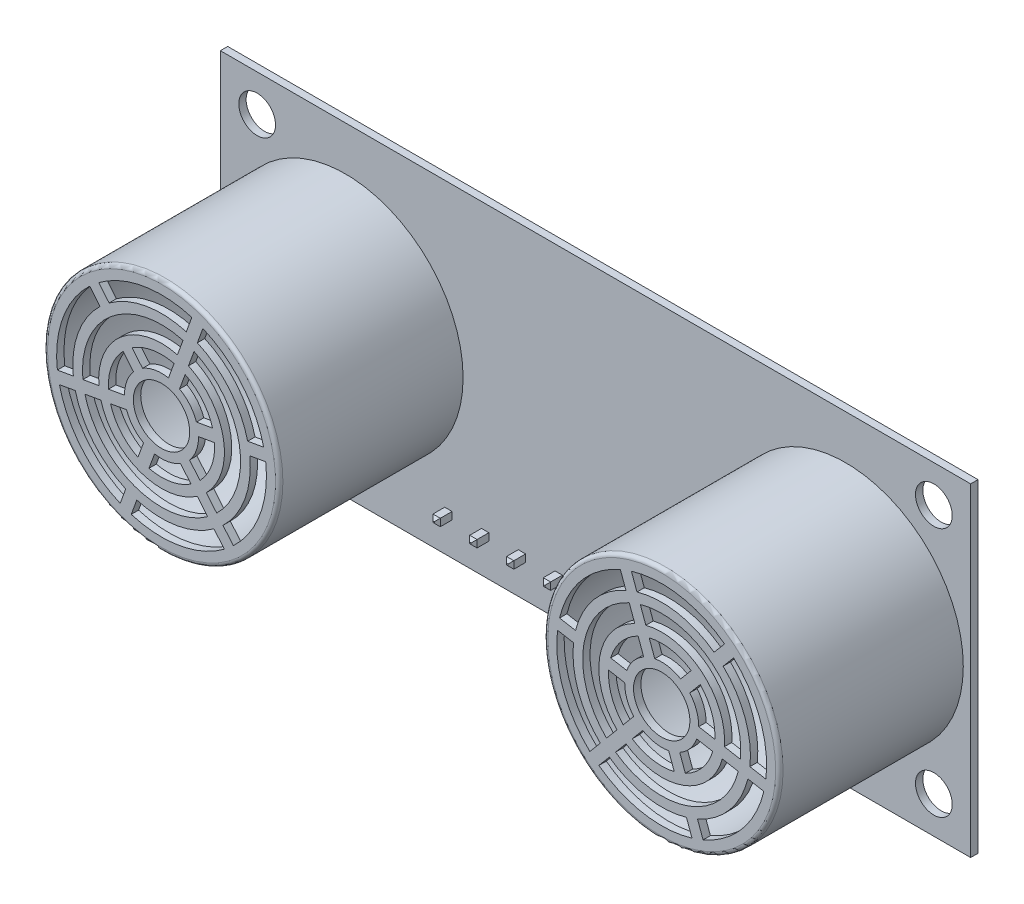
SolidWorks part; units mm, degrees
ref_plane "Спереди" through (0, 0, 0) normal (0, 0, 1) x (1, 0, 0)
ref_plane "Сверху" through (0, 0, 0) normal (0, 1, 0) x (1, 0, 0)
ref_plane "Справа" through (0, 0, 0) normal (1, 0, 0) x (0, 0, -1)
sketch "Эскиз1" plane through (0, 0, 0) normal (0, 0, 1) x (1, 0, 0)
  line L0 (-25.5, 0) -> (25.5, 0) construction
  line L1 (-25.5, -11) -> (25.5, -11)
  line L2 (-25.5, -11) -> (-25.5, 11)
  line L3 (-25.5, 11) -> (25.5, 11)
  line L4 (25.5, -11) -> (25.5, 11)
  line L5 (0, 11) -> (0, -11) construction
  circle A0 centre (-23, 8.5) radius 1.25
  circle A1 centre (-23, -8.5) radius 1.25
  circle A2 centre (23, 8.5) radius 1.25
  circle A3 centre (23, -8.5) radius 1.25
  point P0 (0, 0)
  point P8 (0, 0)
  dimension "D5" = 2.5
  dimension "D1" = 22
  dimension "D2" = 51
  dimension "D3" = 17
  dimension "D4" = 46
extrude "Бобышка-Вытянуть1" add sketch "Эскиз1" against normal blind 0.5
sketch "Эскиз2" plane through (0, 0, 0) normal (0, 0, 1) x (1, 0, 0)
  line L0 (-17, 0) -> (17, 0) construction
  circle A0 centre (-17, 0) radius 8
  dimension "D1" = 16
  dimension "D2" = 34
extrude "Бобышка-Вытянуть2" add sketch "Эскиз2" along normal offset from surface (12.5 mm away) 13 separate body up to face at (24.25, -8.5, -0.5)
shell "Оболочка1" thickness 0.5 removed face at (-9, 0, 0)
sketch "Эскиз3" plane through (0, 0, 12.5) normal (0, 0, 1) x (1, 0, 0)
  circle A1 centre (-17, 0) radius 6.0315
  circle A3 centre (-17, 0) radius 2.5149
  circle A4 centre (-17, 0) radius 4.2741
extrude "Вырез-Вытянуть-Тонкостенный1" cut sketch "Эскиз3" against normal up to next (0.5 mm away) thin contours A4 | A1 | A3 thin type one direction wall 1.1
sketch "Эскиз4" plane through (0, 0, 12.5) normal (0, 0, 1) x (1, 0, 0)
  line L0 (-17, 0) -> (-12.416, -5.463)
  line L1 (-17, 0) -> (-13.44, 0.6277)
  line L2 (-11.7075, 0.9332) -> (-9.9769, 1.2384)
  line L3 (-25.5, -11) -> (25.5, -11) construction
  circle A1 centre (-17, 0) radius 7.1315 construction
  circle A2 centre (-17, 0) radius 3.6149 construction
  circle A4 centre (-17, 0) radius 5.3741 construction
  dimension "D1" = 60
  dimension "D2" = 10
extrude "Вытянуть-Тонкостенный3" add sketch "Эскиз4" against normal blind 0.5 thin thin type mid plane wall 0.8
pattern_circular "Круговой массив2" count 3 over 360 about axis through (-17, 0, 0) along (0, 0, 1) of "Вытянуть-Тонкостенный3"
fillet "Скругление1" radius 0.25 1 edges at (-25, 0, 12.5)
sketch "Эскиз5" plane through (0, 0, 12.5) normal (0, 0, 1) x (1, 0, 0)
  circle A0 centre (-17, 0) radius 1.9149
  arc A1 (-16.5267, 2.47) -> (-18.2896, 2.1591) centre (-17, 0) ccw construction
  dimension "D1" = 0.6
extrude "Вырез-Вытянуть1" cut sketch "Эскиз5" against normal up to next (0.5 mm away)
mirror "Зеркальное отражение1" about plane through (0, 0, 0) normal (1, 0, 0) of bodies 112
sketch "Эскиз6" plane through (0, 0, 0) normal (0, 0, 1) x (1, 0, 0)
  line L0 (0, -8.5) -> (0, 0) construction
  line L1 (-0.25, -8.75) -> (0.25, -8.75)
  line L2 (-0.25, -8.75) -> (-0.25, -8.25)
  line L3 (-0.25, -8.25) -> (0.25, -8.25)
  line L4 (0.25, -8.75) -> (0.25, -8.25)
  line L5 (-0.25, -8.75) -> (0.25, -8.25) construction
  line L6 (-0.25, -8.25) -> (0.25, -8.75) construction
  line L7 (-1.25, -9.75) -> (1.25, -9.75)
  line L8 (-1.25, -9.75) -> (-1.25, -7.25)
  line L9 (-1.25, -7.25) -> (1.25, -7.25)
  line L10 (1.25, -9.75) -> (1.25, -7.25)
  line L11 (-1.25, -9.75) -> (1.25, -7.25) construction
  line L12 (-1.25, -7.25) -> (1.25, -9.75) construction
  line L13 (-25.5, -11) -> (25.5, -11) construction
  point P0 (0, -8.5)
  point P5 (0, -8.5)
  dimension "D1" = 0.5
  dimension "D2" = 2.5
  dimension "D3" = 2.5
  dimension "D4" = 2.5
extrude "Бобышка-Вытянуть3" add sketch "Эскиз6" against normal blind 2 from surface separate body starting at face at (24.25, -8.5, -0.5)
extrude "Бобышка-Вытянуть5" add sketch "Эскиз6<2>" along normal blind 1 and the other way blind 10 separate body contours L1 L4 L3 L2 region at (0, -8.5, 0)
sketch "Эскиз6<2>" plane through (0, 0, 0) normal (0, 0, 1) x (1, 0, 0) same geometry as "Эскиз6"
chamfer "Фаска1" distance 0.2 angle 45 8 edges at (0.25, -8.5, 1) (0, -8.25, 1) (-0.25, -8.5, 1) (0, -8.75, 1) (0.25, -8.5, -10) (0, -8.25, -10) (-0.25, -8.5, -10) (0, -8.75, -10)
pattern_linear "Линейный массив1" count 5 spacing 2.5 along (1, 0, 0) count 5 spacing 2.5 along (-1, 0, 0) of bodies 115 114
